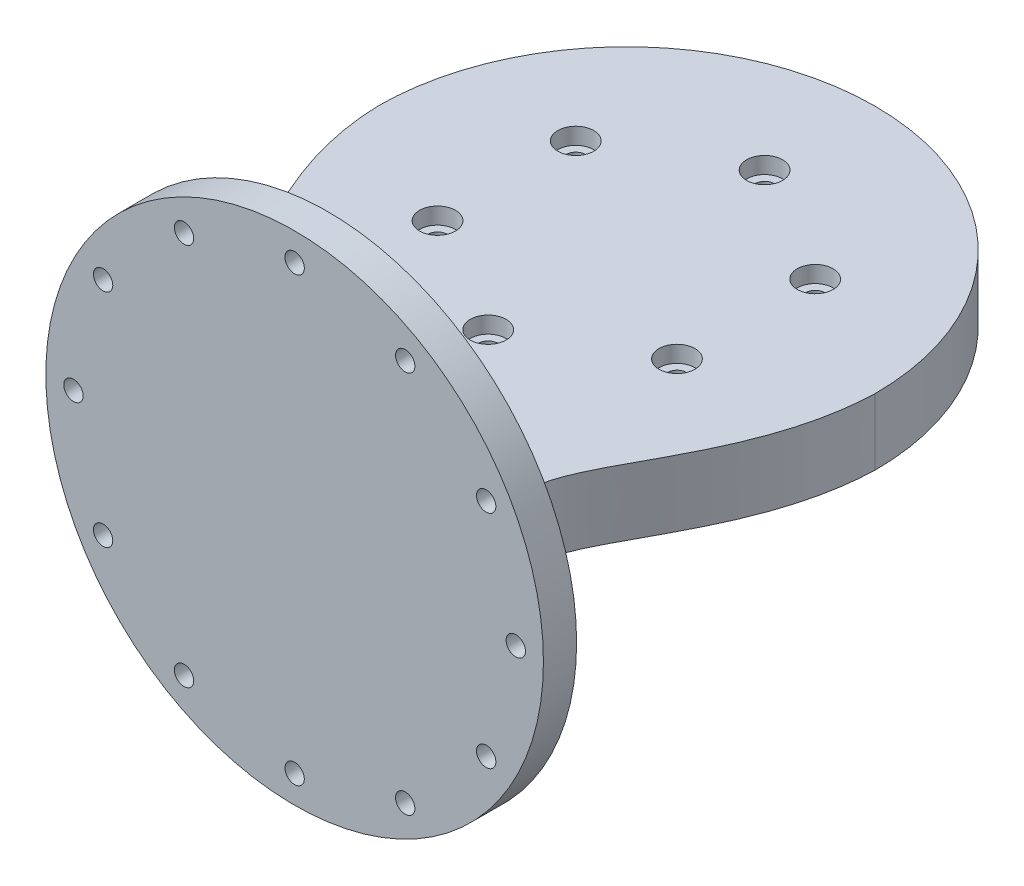
SolidWorks part; units mm, degrees
ref_plane "Front Plane" through (0, 0, 0) normal (0, 0, 1) x (1, 0, 0)
ref_plane "Top Plane" through (0, 0, 0) normal (0, 1, 0) x (1, 0, 0)
ref_plane "Right Plane" through (0, 0, 0) normal (1, 0, 0) x (0, 0, -1)
sketch "Sketch1" plane through (0, 0, 0) normal (0, 1, 0) x (1, 0, 0)
  circle A0 centre (0, 0) radius 45
  dimension "D1" = 90
extrude "Boss-Extrude1" add sketch "Sketch1" along normal blind 12
sketch "Sketch2" plane through (0, 0, 0) normal (0, -1, 0) x (1, 0, 0)
  circle A0 centre (0, 0) radius 35
  dimension "D1" = 70
extrude "Cut-Extrude1" cut sketch "Sketch2" against normal blind 6
sketch "Sketch3" plane through (0, 12, 0) normal (0, 1, 0) x (1, 0, 0)
  line L0 (0, 0) -> (0, -25) construction
  circle A0 centre (0, 0) radius 25 construction
  circle A1 centre (0, -25) radius 1.75
  circle A2 centre (-21.6506, -12.5) radius 1.75
  circle A3 centre (-21.6506, 12.5) radius 1.75
  circle A4 centre (0, 25) radius 1.75
  circle A5 centre (21.6506, 12.5) radius 1.75
  circle A6 centre (21.6506, -12.5) radius 1.75
  point P17 (0, 0)
  dimension "D1" = 50
  dimension "D2" = 3.5
  dimension "D3" = 6
extrude "Cut-Extrude2" cut sketch "Sketch3" against normal through all
sketch "Sketch4" plane through (0, 12, 0) normal (0, 1, 0) x (1, 0, 0)
  circle A0 centre (0, 25) radius 3.25
  circle A1 centre (21.6506, 12.5) radius 3.25
  circle A2 centre (21.6506, -12.5) radius 3.25
  circle A3 centre (0, -25) radius 3.25
  circle A4 centre (-21.6506, -12.5) radius 3.25
  circle A5 centre (-21.6506, 12.5) radius 3.25
  point P15 (0, 0)
  dimension "D1" = 6.5
  dimension "D2" = 6
extrude "Cut-Extrude3" cut sketch "Sketch4" against normal blind 3
sketch "Sketch5" plane through (0, 12, 0) normal (0, 1, 0) x (1, 0, 0)
  line L0 (-45, 0) -> (45, 0) construction
  line L1 (0, 0) -> (0, -45) construction
  line L2 (-45, 0) -> (-45, -60)
  line L3 (-45, -60) -> (45, -60)
  line L4 (45, -60) -> (45, 0)
  circle A0 centre (0, 0) radius 45 construction
  arc A1 (-45, 0) -> (45, 0) centre (0, 0) ccw
  circle M14 centre (0, 0) radius 45
  dimension "D1" = 60
extrude "Boss-Extrude3" add sketch "Sketch5" against normal blind 12 contours M14 region at (0, 12, 45.6258)
sketch "Sketch10" plane through (0, 0, 60) normal (0, 0, 1) x (1, 0, 0)
  line L0 (0, 12) -> (0, 0) construction
  line L1 (-45, 12) -> (45, 12) construction
  line L2 (-45, 0) -> (45, 0) construction
  circle A0 centre (0, 0) radius 45
extrude "Boss-Extrude5" add sketch "Sketch10" against normal blind 6
sketch "Sketch11" plane through (0, 0, 60) normal (0, 0, 1) x (1, 0, 0)
  line L0 (0, 0) -> (48.955, 0) construction
  circle A0 centre (0, 0) radius 40 construction
  circle A1 centre (40, 0) radius 1.75
  circle A2 centre (34.641, -20) radius 1.75
  circle A3 centre (20, -34.641) radius 1.75
  circle A4 centre (0, -40) radius 1.75
  circle A5 centre (-20, -34.641) radius 1.75
  circle A6 centre (-34.641, -20) radius 1.75
  circle A7 centre (-40, 0) radius 1.75
  circle A8 centre (-34.641, 20) radius 1.75
  circle A9 centre (-20, 34.641) radius 1.75
  circle A10 centre (0, 40) radius 1.75
  circle A11 centre (20, 34.641) radius 1.75
  circle A12 centre (34.641, 20) radius 1.75
  point P30 (0, 0)
  dimension "D1" = 80
  dimension "D2" = 3.5
  dimension "D3" = 12
sketch "Sketch14" plane through (0, 0, 0) normal (0, -1, 0) x (1, 0, 0)
  line L1 (45, 0) -> (44.1165, 28.3271) construction
  line L2 (44.1165, 28.3271) -> (18.578, 44.1158) construction
  line L3 (18.578, 44.1158) -> (33.2475, 54) construction
  line L4 (-45, 54) -> (45, 54) construction
  line L6 (45, 0) -> (45, 54)
  line L7 (45, 54) -> (33.2475, 54)
  line L8 (0, 0) -> (0, 60) construction
  line L9 (-45, 0) -> (-44.1165, 28.3271) construction
  line L10 (-44.1165, 28.3271) -> (-18.578, 44.1158) construction
  line L11 (-18.578, 44.1158) -> (-33.2475, 54) construction
  line L12 (-45, 54) -> (-33.2475, 54)
  line L13 (-45, 0) -> (-45, 54)
  circle A0 centre (0, 0) radius 45 construction
  spline S0 degree 3 poles (45, 0) (44.1165, 28.3271) (18.578, 44.1158) (33.2475, 54) knots 0 0 0 0 1 1 1 1
  spline S1 degree 3 poles (-45, 0) (-44.1165, 28.3271) (-18.578, 44.1158) (-33.2475, 54) knots 0 0 0 0 1 1 1 1
  dimension "D1" = 90
sketch "Sketch17" plane through (45, 0, 0) normal (1, 0, 0) x (0, 0, -1)
  line L0 (45, 6) -> (-60, 6) construction
  line L1 (-49, 0) -> (-54, 0)
  line L2 (-54, 0) -> (0, 0) construction
  line L3 (45, 0) -> (45, 12) construction
  line L4 (-60, 40) -> (-60, -40) construction
  line L5 (-54, 0) -> (-54, -5)
  line L8 (-54, -45) -> (-54, 0) construction
  line L9 (-54, 12) -> (-54, 17)
  line L10 (-49, 12) -> (-54, 12)
  arc A0 (-49, 0) -> (-54, -5) centre (-49, -5) ccw
  arc A1 (-49, 12) -> (-54, 17) centre (-49, 17) cw
  line M2 (0, 12) -> (-60, 12)
  line M5 (-54, 0) -> (0, 0)
  dimension "D3" = 5
  dimension "D1" = 5
  dimension "D2" = 5
extrude "Boss-Extrude7" add sketch "Sketch17" against normal through all contours L9 M2 | M5 region at (45, -1.1168, 52.8832) region at (45, 13.1168, 52.8832)
extrude "Cut-Extrude14" cut sketch "Sketch14" against normal through all both and the other way through all
extrude "Cut-Extrude15" cut sketch "Sketch11" against normal up to next
sketch "Sketch18" plane through (0, 0, 54) normal (0, 0, -1) x (-1, 0, 0)
  circle A0 centre (0, 40) radius 3.25
  circle A1 centre (20, 34.641) radius 3.25
  circle A2 centre (34.641, 20) radius 3.25
  circle A3 centre (40, 0) radius 3.25
  circle A4 centre (34.641, -20) radius 3.25
  circle A5 centre (20, -34.641) radius 3.25
  circle A6 centre (0, -40) radius 3.25
  circle A7 centre (-20, -34.641) radius 3.25
  circle A8 centre (-34.641, -20) radius 3.25
  circle A9 centre (-40, 0) radius 3.25
  circle A10 centre (-34.641, 20) radius 3.25
  circle A11 centre (-20, 34.641) radius 3.25
  point P27 (0, 0)
  dimension "D1" = 6.5
  dimension "D2" = 12
extrude "Cut-Extrude16" cut sketch "Sketch18" against normal blind 3
sketch "Sketch19" plane through (0, 0, 54) normal (0, 0, -1) x (-1, 0, 0)
  line L0 (45, 0) -> (-45, 0) construction
  line L1 (-45, 0) -> (45, 0) construction
  line L2 (-45, 0) -> (-45, 12) construction
  line L3 (0, 0) -> (0, 54.4625) construction
  circle A0 centre (-34.641, 20) radius 6
  circle A1 centre (34.641, 20) radius 6
  circle A2 centre (-34.641, -20) radius 6
  circle A3 centre (34.641, -20) radius 6
  dimension "D1" = 12
extrude "Cut-Extrude17" cut sketch "Sketch19" along normal through all
sketch "Sketch20" plane through (0, 0, 60) normal (0, 0, 1) x (1, 0, 0)
  line L0 (-45, 12) -> (-43.3705, 12) construction
  line L1 (-43.3705, 12) -> (-45, 12)
  line L2 (-45, 12) -> (-45, 0)
  line L3 (0, 0) -> (0, 45) construction
  line L4 (45, 12) -> (45, 0)
  line L5 (43.3705, 12) -> (45, 12)
  arc A0 (-45, 0) -> (-43.3705, 12) centre (0, 0) cw
  arc A1 (43.3705, 12) -> (-43.3705, 12) centre (0, 0) ccw construction
  arc A2 (45, 0) -> (43.3705, 12) centre (0, 0) ccw
extrude "Cut-Extrude18" cut sketch "Sketch20" against normal up to next
